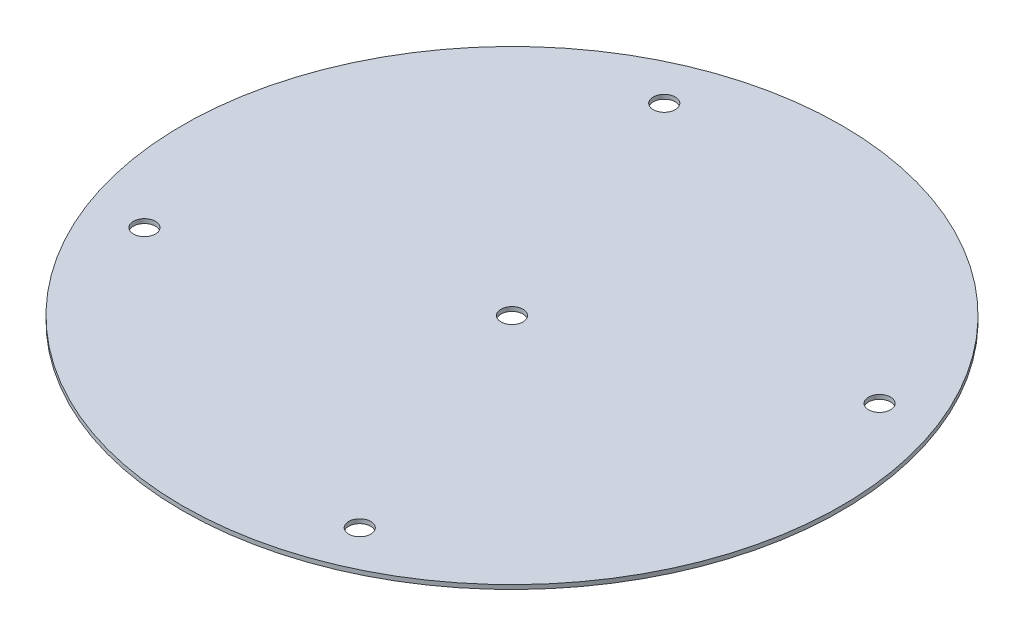
SolidWorks part; units mm, degrees
material "6061-T6 (SS)"
ref_plane "Front Plane" through (0, 0, 0) normal (0, 0, 1) x (1, 0, 0)
ref_plane "Top Plane" through (0, 0, 0) normal (0, 1, 0) x (1, 0, 0)
ref_plane "Right Plane" through (0, 0, 0) normal (1, 0, 0) x (0, 0, -1)
sketch "Sketch2" plane through (0, 0, 0) normal (1, 0, 0) x (0, 0, -1)
  line L0 (0, 0) -> (-77.55, 0)
  line L1 (-77.55, 0) -> (-77.55, 1)
  line L2 (-77.55, 1) -> (0, 1)
  line L5 (0, 1) -> (0, 0)
  dimension "D1" = 77.55
  dimension "D2" = 1
ref_axis "Axis1" through (0, -0.05, 0) along (0, 1, 0)
revolve "Revolve1" add sketch "Sketch2" angle 360 about axis through (0, -0.05, 0) along (0, 1, 0)
hole_wizard "#6 (0.204) Diameter Hole1" positions "Sketch6" profile "Sketch7" hole size "#6" standard "ANSI Inch" end condition through all
sketch "Sketch6" plane through (0, 1, 0) normal (0, 1, 0) x (1, 0, 0)
  line L0 (0, 0) -> (-53.438, 129.0108) construction
  line L2 (0, 0) -> (0, 109.0908) construction
  point P0 (-25.3336, 61.1608)
  dimension "D1" = 22.5
  dimension "D2" = 66.2
sketch "Sketch7" plane through (-25.3336, 1, -61.1608) normal (1, 0, 0) x (0, 0, 1)
  line L0 (0, 0) -> (0, 1)
  line L1 (0, 1) -> (2.5908, 1)
  line L2 (2.5908, 1) -> (2.5908, 0)
  line L5 (2.5908, 0) -> (0, 0)
  line L11 (0, -6.35) -> (0, 107.95) construction
  dimension "Thru Hole Dia." = 5.1816
  dimension "Thru Hole Depth" = 1
pattern_circular "CirPattern3" count 4 over 360 about axis through (0, -0.05, 0) along (0, 1, 0) of "#6 (0.204) Diameter Hole1"
hole_wizard "#6 (0.204) Diameter Hole2" positions "Sketch8" profile "Sketch9" hole size "#6" standard "ANSI Inch" end condition through all
sketch "Sketch8" plane through (0, 1, 0) normal (0, 1, 0) x (1, 0, 0)
  line L0 (0, 0) -> (106.3094, -1.7118) construction
  point P7 (0, 0)
sketch "Sketch9" plane through (0, 1, 0) normal (1, 0, 0) x (0, 0, 1)
  line L0 (0, 0) -> (0, 1)
  line L1 (0, 1) -> (2.5908, 1)
  line L2 (2.5908, 1) -> (2.5908, 0)
  line L5 (2.5908, 0) -> (0, 0)
  line L11 (0, -6.35) -> (0, 107.95) construction
  dimension "Thru Hole Dia." = 5.1816
  dimension "Thru Hole Depth" = 1
equation "\"TubeDiameter\" = 6.500in"
equation "\"D1@Sketch2\"=\"TubeDiameter\"/2-5mm"
equation "\"D2@Sketch6\"=66.2"
